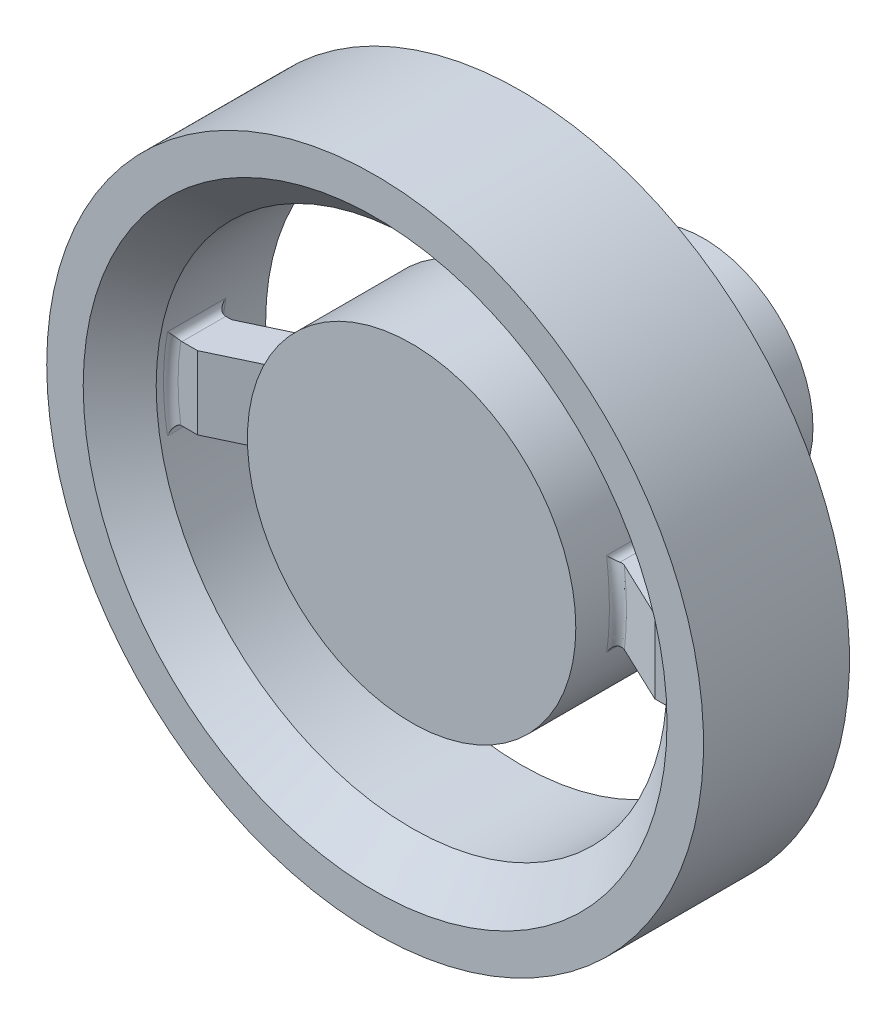
SolidWorks part; units mm, degrees
ref_plane "Front Plane" through (0, 0, 0) normal (0, 0, 1) x (1, 0, 0)
ref_plane "Top Plane" through (0, 0, 0) normal (0, 1, 0) x (1, 0, 0)
ref_plane "Right Plane" through (0, 0, 0) normal (1, 0, 0) x (0, 0, -1)
sketch "Sketch1" plane through (0, 0, 0) normal (0, 0, 1) x (1, 0, 0)
  circle A0 centre (0, 0) radius 15
  circle A1 centre (0, 0) radius 7.5
  dimension "D1" = 30
  dimension "D2" = 15
extrude "Eixo" add sketch "Sketch1" along normal blind 40
sketch "Sketch2" plane through (0, 0, 40) normal (0, 0, 1) x (1, 0, 0)
  circle A0 centre (0, 0) radius 22.5
  dimension "D1" = 45
extrude "Encaixe do Manípulo" add sketch "Sketch2" against normal blind 15
sketch "Sketch3" plane through (0, 0, 25) normal (0, 0, -1) x (-1, 0, 0)
  circle A0 centre (0, 0) radius 45
  circle A1 centre (0, 0) radius 35
  dimension "D1" = 90
  dimension "D2" = 10
extrude "Boss-Extrude3" add sketch "Sketch3" against normal blind 20 separate body
sketch "Sketch4" plane through (0, 0, 0) normal (0, 1, 0) x (1, 0, 0)
  line L0 (-22.5, -40) -> (22.5, -40) construction
  line L1 (22.5, -25) -> (-22.5, -25) construction
  line L2 (-22.5, -40) -> (22.5, -40) construction
  line L3 (22.5, -25) -> (-22.5, -25) construction
  line L4 (-22.5, -25) -> (-22.5, -40) construction
  line L5 (22.5, -25) -> (22.5, -40) construction
  line L6 (45, -25) -> (-45, -25) construction
  line L7 (-45, -45) -> (45, -45) construction
  line L8 (45, -25) -> (-45, -25) construction
  line L9 (-45, -45) -> (45, -45) construction
  line L10 (-45, -45) -> (-45, -25) construction
  line L11 (45, -45) -> (45, -25) construction
  line L12 (0, -25) -> (0, -45) construction
  line L13 (22.5, -30.5) -> (32, -35) construction
  line L18 (32, -35) -> (42, -35) construction
  line L19 (45, -35) -> (42, -35) construction
  line L20 (19.5, -32.3985) -> (31.3254, -38)
  line L22 (31.3254, -38) -> (42, -38)
  line L23 (19.5, -25.7594) -> (19.5, -32.3985)
  line L26 (42, -38) -> (42, -32)
  line L27 (42, -45) -> (42, -25) construction
  line L28 (19.5, -25.7594) -> (32.6746, -32)
  line L29 (32.6746, -32) -> (42, -32)
  line L30 (23.7843, -27.7888) -> (32.6746, -32) construction
  line L31 (21.2157, -33.2112) -> (31.3254, -38) construction
  line L32 (-32, -35) -> (-42, -35) construction
  line L33 (-32.6746, -32) -> (-42, -32)
  line L34 (-31.3254, -38) -> (-42, -38)
  line L35 (-19.5, -25.7594) -> (-32.6746, -32)
  line L36 (-19.5, -32.3985) -> (-31.3254, -38)
  line L37 (-22.5, -30.5) -> (-32, -35) construction
  line L38 (-19.5, -25.7594) -> (-19.5, -32.3985)
  line L39 (-42, -32) -> (-42, -38)
  point P21 (22.5, -32.5)
  dimension "D5" = 3
  dimension "D1" = 3
  dimension "D2" = 10
  dimension "D3" = 2
  dimension "D4" = 3
  dimension "D6" = 3
extrude "Boss-Extrude4" add sketch "Sketch4" along normal mid plane 10 contours L33 L39 L34 L36 L38 L35 | L29 L28 L23 L20 L22 L26 region at (30.471, 0, 33.2771) region at (-30.471, 0, 33.2771)
chamfer "Chanfros de 5x45°" distance 5 angle 45 2 edges at (-35, 0, 45) (15, 0, 25)
fillet "Raios 1mm" radius 1 16 edges at (21.9374, 5, 30.2335) (22.5, 0, 27.1805) (35, 0, 32) (21.9374, -5, 30.2335) (22.5, 0, 33.8195) (34.641, 5, 35) (34.641, -5, 35) (35, 0, 38) (-21.9374, 5, 30.2335) (-22.5, 0, 27.1805) (-35, 0, 32) (-21.9374, -5, 30.2335) (-22.5, 0, 33.8195) (-34.641, -5, 35) (-34.641, 5, 35) (-35, 0, 38)
ref_plane "Plano de Referência" through (0, 15, 0) normal (0, 1, 0) x (1, 0, 0)
sketch "Sketch5" plane through (0, 15, 0) normal (0, 1, 0) x (1, 0, 0)
  line L0 (0, 0) -> (0, -20) construction
  line L1 (15, -20) -> (-15, -20) construction
  circle A0 centre (0, -10) radius 1.5
  dimension "D1" = 3
extrude "Furo Ø3 Passante" cut sketch "Sketch5" against normal through all
